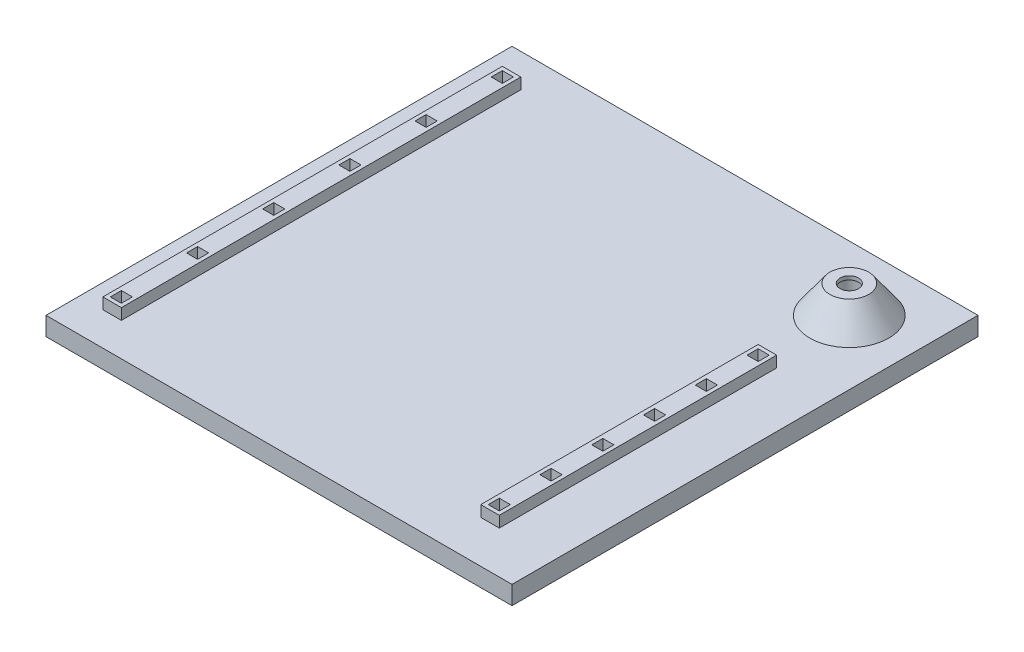
SolidWorks part; units mm, degrees
ref_plane "Front Plane" through (0, 0, 0) normal (0, 0, 1) x (1, 0, 0)
ref_plane "Top Plane" through (0, 0, 0) normal (0, 1, 0) x (1, 0, 0)
ref_plane "Right Plane" through (0, 0, 0) normal (1, 0, 0) x (0, 0, -1)
sketch "Sketch1" plane through (0, 0, 0) normal (0, 1, 0) x (1, 0, 0)
  line L1 (0, 0) -> (126, 0)
  line L2 (0, 0) -> (0, 126)
  line L3 (0, 126) -> (126, 126)
  line L4 (126, 0) -> (126, 126)
  dimension "D1" = 126
  dimension "D2" = 126
extrude "Boss-Extrude1" add sketch "Sketch1" along normal blind 5
sketch "Sketch3" plane through (0, 5, 0) normal (0, 1, 0) x (1, 0, 0)
  line L0 (108.6, 121.1) -> (108.6, 96.1) construction
  circle A0 centre (108.6, 108.6) radius 12.5
extrude "Boss-Extrude2" add sketch "Sketch3" along normal blind 7.5
sketch "Sketch4" plane through (0, 0, 0) normal (0, -1, 0) x (1, 0, 0)
  circle A1 centre (108.6, -108.6) radius 2.95
  dimension "D1" = 5.9
extrude "Cut-Extrude1" cut sketch "Sketch4" against normal blind 11.5
sketch "Sketch6" plane through (0, 12.5, 0) normal (0, 1, 0) x (1, 0, 0)
  line L0 (108.6, 121.1) -> (108.6, 96.1) construction
  circle A0 centre (108.6, 108.6) radius 12.5 construction
  circle A1 centre (108.6, 108.6) radius 2.5
  dimension "D1" = 5
extrude "Cut-Extrude2" cut sketch "Sketch6" against normal through all
chamfer "Chamfer1" distance 10 angle 36 1 edges at (108.6, 12.5, -96.1) first distance on face at (108.6, 12.5, -96.1)
sketch "Sketch9" plane through (0, 5, 0) normal (0, 1, 0) x (1, 0, 0)
  line L1 (111.1, 11.4582) -> (106.1, 11.4582)
  line L2 (0, 0) -> (126, 0) construction
  line L3 (111.1, 11.4582) -> (111.1, 86.4582)
  line L4 (108.6, 97.9164) -> (108.6, 0)
  line L5 (111.1, 86.4582) -> (106.1, 86.4582)
  line L6 (106.1, 11.4582) -> (106.1, 86.4582)
  line L7 (111.1, 11.4582) -> (106.1, 86.4582) construction
  line L8 (111.1, 86.4582) -> (106.1, 11.4582) construction
  circle A0 centre (108.6, 108.6) radius 10.6836 construction
  point P0 (108.6, 48.9582)
  point P5 (115.3692, 53.7951)
  dimension "D1" = 75
  dimension "D2" = 5
extrude "Boss-Extrude4" add sketch "Sketch9" along normal blind 3 contours L3 L5 L6 L1
sketch "Sketch10" plane through (0, 8, 0) normal (0, 1, 0) x (1, 0, 0)
  line L0 (108.6, 86.4582) -> (108.6, 11.4582) construction
  line L1 (111.1, 86.4582) -> (106.1, 86.4582) construction
  line L2 (111.1, 11.4582) -> (106.1, 11.4582) construction
  line L9 (110.1, 82.4582) -> (107.1, 82.4582)
  line L10 (110.1, 82.4582) -> (110.1, 85.4582)
  line L11 (110.1, 85.4582) -> (107.1, 85.4582)
  line L12 (107.1, 82.4582) -> (107.1, 85.4582)
  line L13 (110.1, 82.4582) -> (107.1, 85.4582) construction
  line L14 (110.1, 85.4582) -> (107.1, 82.4582) construction
  line L18 (110.1, 68.4589) -> (110.1, 71.4589)
  line L19 (110.1, 71.4589) -> (107.1, 71.4589)
  line L20 (107.1, 68.4589) -> (107.1, 71.4589)
  line L21 (110.1, 68.4589) -> (107.1, 68.4589)
  line L22 (110.1, 54.4597) -> (110.1, 57.4597)
  line L23 (110.1, 57.4597) -> (107.1, 57.4597)
  line L24 (107.1, 54.4597) -> (107.1, 57.4597)
  line L25 (110.1, 54.4597) -> (107.1, 54.4597)
  line L26 (110.1, 40.4604) -> (110.1, 43.4604)
  line L27 (110.1, 43.4604) -> (107.1, 43.4604)
  line L28 (107.1, 40.4604) -> (107.1, 43.4604)
  line L29 (110.1, 40.4604) -> (107.1, 40.4604)
  line L30 (110.1, 26.4612) -> (110.1, 29.4612)
  line L31 (110.1, 29.4612) -> (107.1, 29.4612)
  line L32 (107.1, 26.4612) -> (107.1, 29.4612)
  line L33 (110.1, 26.4612) -> (107.1, 26.4612)
  line L34 (110.1, 12.4619) -> (110.1, 15.4619)
  line L35 (110.1, 15.4619) -> (107.1, 15.4619)
  line L36 (107.1, 12.4619) -> (107.1, 15.4619)
  line L37 (110.1, 12.4619) -> (107.1, 12.4619)
  point P12 (0, 0)
  point P13 (108.6, 83.9582)
  dimension "D2" = 3
  dimension "D3" = 3
  dimension "D4" = 6
extrude "Cut-Extrude4" cut sketch "Sketch10" against normal through all
sketch "Sketch11" plane through (0, 5, 0) normal (0, 1, 0) x (1, 0, 0)
  line L5 (8.8811, 126) -> (8.8811, 0) construction
  line L7 (11.3811, 9) -> (6.3811, 9)
  line L8 (11.3811, 9) -> (11.3811, 117)
  line L9 (11.3811, 117) -> (6.3811, 117)
  line L10 (6.3811, 9) -> (6.3811, 117)
  line L11 (11.3811, 9) -> (6.3811, 117) construction
  line L12 (11.3811, 117) -> (6.3811, 9) construction
  point P9 (8.8811, 63)
  dimension "D1" = 108
  dimension "D2" = 5
extrude "Boss-Extrude5" add sketch "Sketch11" along normal blind 3
sketch "Sketch12" plane through (0, 8, 0) normal (0, 1, 0) x (1, 0, 0)
  line L5 (8.8811, 117) -> (8.8811, 112) construction
  line L7 (10.3811, 113) -> (7.3811, 113)
  line L8 (10.3811, 113) -> (10.3811, 116)
  line L9 (10.3811, 116) -> (7.3811, 116)
  line L10 (7.3811, 113) -> (7.3811, 116)
  line L11 (10.3811, 113) -> (7.3811, 116) construction
  line L12 (10.3811, 116) -> (7.3811, 113) construction
  line L17 (10.3811, 95.4002) -> (7.3811, 95.4002)
  line L18 (7.3811, 92.4002) -> (7.3811, 95.4002)
  line L19 (10.3811, 92.4002) -> (7.3811, 92.4002)
  line L20 (10.3811, 92.4002) -> (10.3811, 95.4002)
  line L21 (10.3811, 74.8003) -> (7.3811, 74.8003)
  line L22 (7.3811, 71.8003) -> (7.3811, 74.8003)
  line L23 (10.3811, 71.8003) -> (7.3811, 71.8003)
  line L24 (10.3811, 71.8003) -> (10.3811, 74.8003)
  line L25 (10.3811, 54.2005) -> (7.3811, 54.2005)
  line L26 (7.3811, 51.2005) -> (7.3811, 54.2005)
  line L27 (10.3811, 51.2005) -> (7.3811, 51.2005)
  line L28 (10.3811, 51.2005) -> (10.3811, 54.2005)
  line L29 (10.3811, 33.6007) -> (7.3811, 33.6007)
  line L30 (7.3811, 30.6007) -> (7.3811, 33.6007)
  line L31 (10.3811, 30.6007) -> (7.3811, 30.6007)
  line L32 (10.3811, 30.6007) -> (10.3811, 33.6007)
  line L33 (10.3811, 13.0008) -> (7.3811, 13.0008)
  line L34 (7.3811, 10.0008) -> (7.3811, 13.0008)
  line L35 (10.3811, 10.0008) -> (7.3811, 10.0008)
  line L36 (10.3811, 10.0008) -> (10.3811, 13.0008)
  point P9 (8.8811, 114.5)
  dimension "D2" = 3
  dimension "D3" = 3
  dimension "D4" = 6
extrude "Cut-Extrude5" cut sketch "Sketch12" against normal through all
